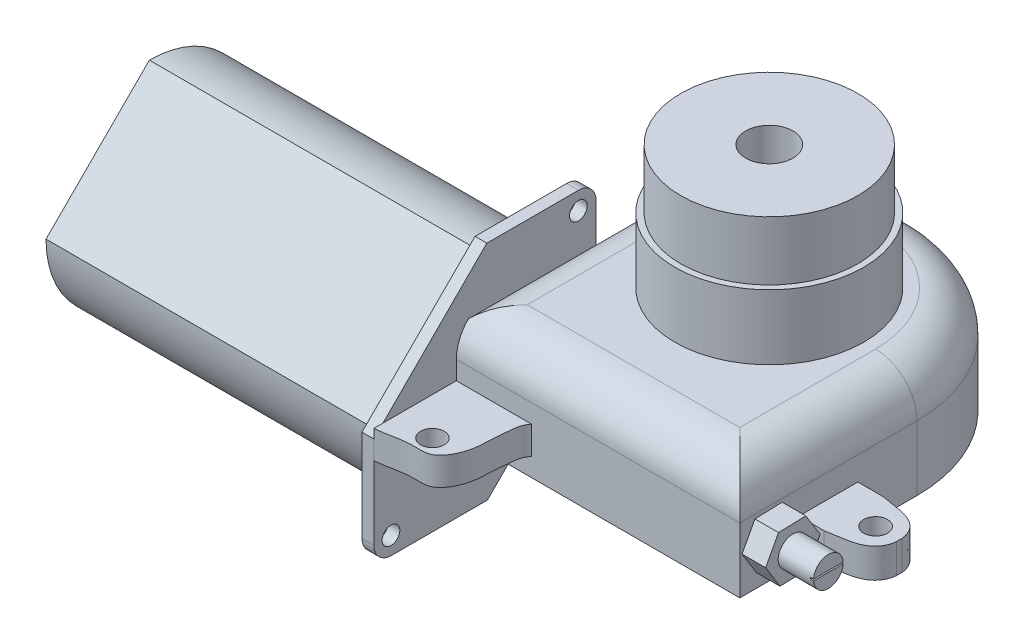
SolidWorks part; units mm, degrees
ref_plane "Front Plane" through (0, 0, 0) normal (0, 0, 1) x (1, 0, 0)
ref_plane "Top Plane" through (0, 0, 0) normal (0, 1, 0) x (1, 0, 0)
ref_plane "Right Plane" through (0, 0, 0) normal (1, 0, 0) x (0, 0, -1)
sketch "Sketch2" plane through (0, 0, 0) normal (0, 0, 1) x (1, 0, 0)
  line L1 (-25, -9) -> (25, -9)
  line L2 (-25, -9) -> (-25, 9)
  line L3 (-25, 9) -> (25, 9)
  line L4 (25, -9) -> (25, 9)
  line L5 (-25, -9) -> (25, 9) construction
  line L6 (-25, 9) -> (25, -9) construction
  point P0 (0, 0)
  dimension "D1" = 50
  dimension "D2" = 18
extrude "Boss-Extrude1" add sketch "Sketch2" against normal blind 60
sketch "Sketch3" plane through (0, 9, 0) normal (0, 1, 0) x (1, 0, 0)
  line L0 (0, 60) -> (0, 0) construction
  line L1 (25, 60) -> (-25, 60) construction
  line L2 (-25, 30) -> (-25, 60)
  line L3 (-25, 60) -> (25, 60)
  line L4 (25, 60) -> (25, 30)
  circle A0 centre (0, 30) radius 15
  circle A1 centre (0, 30) radius 25
  line M2 (25, 0) -> (25, 60)
  line M3 (25, 60) -> (-25, 60)
  line M4 (-25, 60) -> (-25, 0)
  dimension "D1" = 30
extrude "Cut-Extrude1" cut sketch "Sketch3" against normal blind 50 contours L0 L3 A1 M4 | L0 A1 M3 M2 region at (16.0797, 9, -53.3155) region at (-16.0797, 9, -53.3155)
sketch "Sketch4" plane through (0, 9, 0) normal (0, 1, 0) x (1, 0, 0)
  circle A0 centre (0, 30) radius 16
extrude "Boss-Extrude2" add sketch "Sketch4" along normal blind 11
sketch "Sketch5" plane through (0, 20, 0) normal (0, 1, 0) x (1, 0, 0)
  circle A0 centre (0, 30) radius 15
extrude "Boss-Extrude3" add sketch "Sketch5" along normal blind 10
sketch "Sketch6" plane through (0, 30, 0) normal (0, 1, 0) x (1, 0, 0)
  circle A0 centre (0, 30) radius 4
extrude "Cut-Extrude2" cut sketch "Sketch6" against normal blind 45
fillet "Fillet1" radius 7 1 edges at (0, 9, 0)
fillet "Fillet6" radius 7 3 edges at (-25, 9, -18.5) (0, 9, -55) (25, 9, -18.5) tangent propagation no
sketch "Sketch7" plane through (25, 0, 0) normal (1, 0, 0) x (0, 0, -1)
  line L0 (0, -9) -> (0, 2) construction
  line L1 (10, -2) -> (20, -2)
  line L2 (10, -2) -> (10, -7)
  line L3 (10, -7) -> (20, -7)
  line L4 (20, -2) -> (20, -7)
  line L5 (30, -9) -> (0, -9) construction
  dimension "D1" = 10
  dimension "D2" = 5
  dimension "D3" = 10
  dimension "D4" = 2
extrude "Boss-Extrude4" add sketch "Sketch7" along normal blind 12
sketch "Sketch8" plane through (0, -7, 0) normal (0, -1, 0) x (-1, 0, 0)
  line L0 (-37, 10) -> (-37, 20) construction
  circle A0 centre (-33, 15) radius 2.018
  dimension "D1" = 4
extrude "Cut-Extrude3" cut sketch "Sketch8" against normal blind 10 contours A0
sketch "Sketch9" plane through (0, -7, 0) normal (0, -1, 0) x (1, 0, 0)
  line L4 (37, -10) -> (25, -10) construction
  line L5 (37, -10) -> (37, -20) construction
  line L6 (37, -15) -> (25, -15) construction
  line L7 (25, -10) -> (25, -20) construction
  line L8 (29.301, -10) -> (37, -10)
  line L9 (37, -10) -> (37, -20)
  line L10 (37, -20) -> (29.301, -20)
  spline S0 degree 3 poles (29.301, -10) (31.159, -10.422) (35.5526, -10.3624) (37.0825, -13.8586) (37, -15) knots 0 0 0 0 0.665986 1 1 1 1
  spline S1 degree 3 poles (29.301, -20) (31.159, -19.578) (35.5526, -19.6376) (37.0825, -16.1414) (37, -15) knots 0 0 0 0 0.665986 1 1 1 1
  line M3 (25, -20) -> (37, -20)
  line M4 (37, -20) -> (37, -10)
  line M5 (37, -10) -> (25, -10)
extrude "Cut-Extrude4" cut sketch "Sketch9" against normal blind 10 contours S1 M3 M4 | S0 M5 M4 region at (35.0308, -7, -19.0517) region at (35.0308, -7, -10.9483)
sketch "Sketch10" plane through (25, 0, 0) normal (1, 0, 0) x (0, 0, -1)
  line L0 (0, -2.622) -> (10, -2.622) construction
  line L1 (0, -9) -> (0, 2) construction
  line L2 (10, -2) -> (10, -7) construction
  line L4 (7.1817, 1.4491) -> (2.5652, 1.303)
  line L5 (2.5652, 1.303) -> (0.3835, -2.7681)
  line L6 (0.3835, -2.7681) -> (2.8183, -6.693)
  line L7 (2.8183, -6.693) -> (7.4348, -6.5469)
  line L8 (7.4348, -6.5469) -> (9.6165, -2.4758)
  line L9 (9.6165, -2.4758) -> (7.1817, 1.4491)
  circle A0 centre (5, -2.622) radius 4 construction
  dimension "D1" = 8
extrude "Boss-Extrude5" add sketch "Sketch10" along normal blind 4
sketch "Sketch12" plane through (29, 0, 0) normal (1, 0, 0) x (0, 0, -1)
  circle A0 centre (5, -2.622) radius 2.5
extrude "Boss-Extrude6" add sketch "Sketch12" against normal blind 73 and the other way blind 6
sketch "Sketch15" plane through (35, 0, 0) normal (1, 0, 0) x (0, 0, -1)
  line L1 (1.8459, -2.7533) -> (8.1541, -2.7533)
  line L2 (1.8459, -2.7533) -> (1.8459, -2.4906)
  line L3 (1.8459, -2.4906) -> (8.1541, -2.4906)
  line L4 (8.1541, -2.7533) -> (8.1541, -2.4906)
  line L5 (1.8459, -2.7533) -> (8.1541, -2.4906) construction
  line L6 (1.8459, -2.4906) -> (8.1541, -2.7533) construction
  point P0 (5, -2.622)
extrude "Cut-Extrude6" cut sketch "Sketch15" against normal blind 0.5
sketch "Sketch16" plane through (-25, 0, 0) normal (-1, 0, 0) x (0, 0, 1)
  line L2 (-5, 14.878) -> (12.5, -2.622)
  line L3 (-22.5, -2.622) -> (-5, -20.122)
  arc A0 (-5, 14.878) -> (-22.5, -2.622) centre (-5, -2.622) ccw
  arc A1 (-5, -20.122) -> (12.5, -2.622) centre (-5, -2.622) ccw
extrude "Boss-Extrude7" add sketch "Sketch16" along normal blind 55
sketch "Sketch19" plane through (-80, 0, 0) normal (-1, 0, 0) x (0, 0, 1)
  line L0 (-5, -20.122) -> (-5, 14.878) construction
sketch "Sketch20" plane through (-80, 0, 0) normal (-1, 0, 0) x (0, 0, 1)
  line L0 (-22.5, -2.622) -> (12.5, -2.622) construction
  arc A0 (-5, -20.122) -> (12.5, -2.622) centre (-5, -2.622) ccw construction
sketch "Sketch22" plane through (-80, 0, 0) normal (-1, 0, 0) x (0, 0, 1)
  line L0 (-5, -20.122) -> (-5, 14.878) construction
  circle A0 centre (-5, -2.622) radius 8.3282
extrude "Boss-Extrude8" add sketch "Sketch22" along normal blind 3
sketch "Sketch23" plane through (-83, 0, 0) normal (-1, 0, 0) x (0, 0, 1)
  line L0 (-5, -20.122) -> (-5, 14.878) construction
  circle A0 centre (-5, -2.622) radius 2.622
extrude "Boss-Extrude9" add sketch "Sketch23" along normal blind 2
fillet "Fillet7" radius 2 1 edges at (-83, -2.622, 3.3282)
fillet "Fillet8" radius 1 1 edges at (-85, -2.622, -2.378)
sketch "Sketch24" plane through (-25, 0, 0) normal (1, 0, 0) x (0, 0, -1)
  line L0 (-13.9803, -2.688) -> (5.1594, 16.4517)
  line L6 (-12.5, -2.622) -> (5, 14.878) construction
  line L7 (5.2558, -21.2804) -> (23.6584, -2.8777)
  line L8 (16.122, -9) -> (5, -20.122) construction
  line L9 (-13.9803, -2.688) -> (-13.9803, -18.2804)
  line L10 (-10.9803, -21.2804) -> (5.2558, -21.2804)
  line L11 (5.1594, 16.4517) -> (20.6584, 16.4517)
  line L12 (23.6584, 13.4517) -> (23.6584, -2.8777)
  arc A2 (20.6584, 16.4517) -> (23.6584, 13.4517) centre (20.6584, 13.4517) cw
  arc A3 (-13.9803, -18.2804) -> (-10.9803, -21.2804) centre (-10.9803, -18.2804) ccw
  dimension "D3" = 3
  dimension "D1" = 1
  dimension "D2" = 1
extrude "Boss-Extrude10" add sketch "Sketch24" along normal blind 2
sketch "Sketch25" plane through (-25, 0, 0) normal (-1, 0, 0) x (0, 0, 1)
  circle A2 centre (-20.6584, 13.4517) radius 1.5
  circle A3 centre (11.0736, -18.2804) radius 1.5
extrude "Cut-Extrude7" cut sketch "Sketch25" against normal blind 2
sketch "Sketch27" plane through (0, 0, 0) normal (0, 0, 1) x (1, 0, 0)
  line L0 (-23, 2) -> (-23, -9) construction
  line L1 (-23, -5.8814) -> (-10.2435, -5.8814)
  line L2 (-23, -5.8814) -> (-23, -1.1433)
  line L3 (-23, -1.1433) -> (-10.2435, -1.1433)
  line L4 (-10.2435, -5.8814) -> (-10.2435, -1.1433)
extrude "Boss-Extrude11" add sketch "Sketch27" along normal blind 14
sketch "Sketch28" plane through (0, -5.8814, 0) normal (0, -1, 0) x (-1, 0, 0)
  circle A0 centre (16.6218, -10.4362) radius 2
  spline S0 degree 3 poles (23, -13.9803) (21.0404, -13.8499) (18.3273, -12.8695) (14.7662, -13.3832) (13.1956, -12.1577) (12.4536, -10.9671) (11.8257, -9.4877) (11.4273, -7.5803) (11.453, -5.4327) (11.1299, -2.7924) (11.0848, -0.9232) (10.2435, 0) knots 0 0 0 0 0.253392 0.384448 0.437711 0.505134 0.567822 0.648625 0.759594 0.849288 1 1 1 1
  line M2 (10.2435, 0) -> (10.2435, -14)
  line M3 (10.2435, -14) -> (23, -14)
  line M4 (23, -14) -> (23, -13.9803)
extrude "Cut-Extrude8" cut sketch "Sketch28" against normal blind 14 contours S0 M4 M2 M3 | A0 region at (-16.6218, -5.8814, 10.4362) region at (-22.8106, -5.8814, 13.9902)
